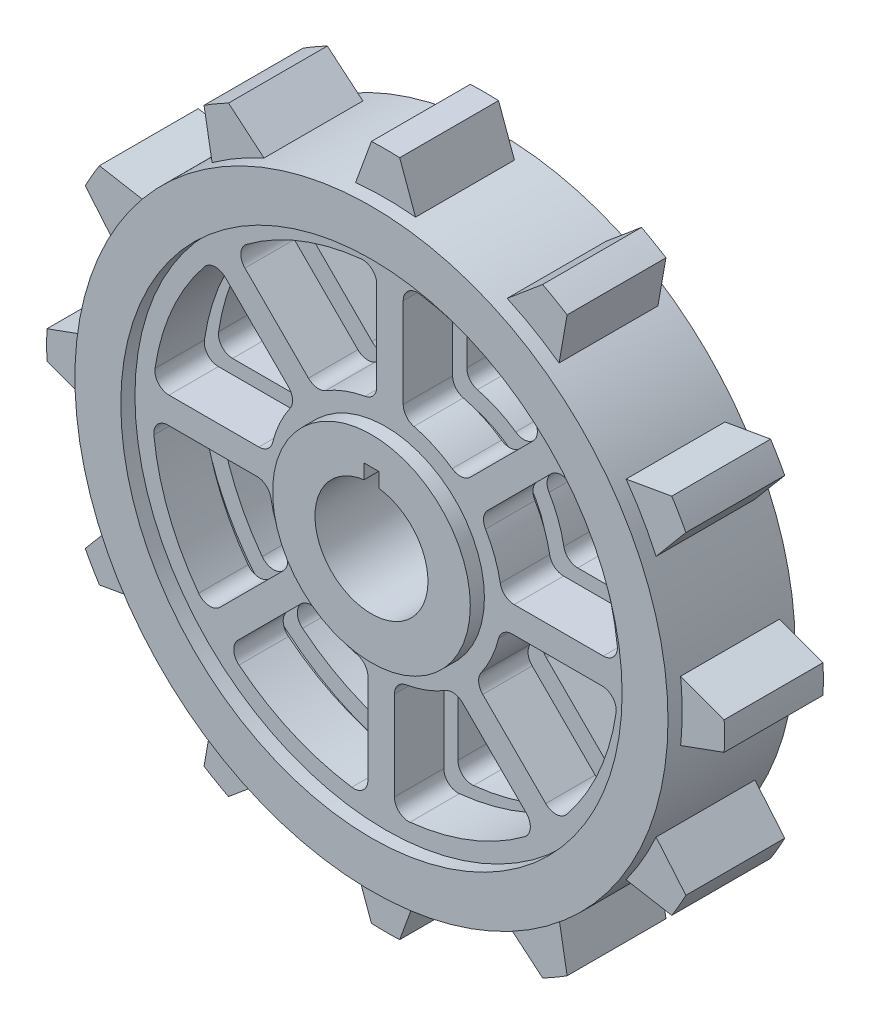
SolidWorks part; units mm, degrees
ref_plane "Front Plane" through (0, 0, 0) normal (0, 0, 1) x (1, 0, 0)
ref_plane "Top Plane" through (0, 0, 0) normal (0, 1, 0) x (1, 0, 0)
ref_plane "Right Plane" through (0, 0, 0) normal (1, 0, 0) x (0, 0, -1)
sketch "Sketch3" plane through (0, 0, 0) normal (0, 0, 1) x (1, 0, 0)
  circle A0 centre (0, 0) radius 21
  dimension "D1" = 42
extrude "Boss-Extrude2" add sketch "Sketch3" along normal mid plane 9
sketch "Sketch4" plane through (0, 0, 4.5) normal (0, 0, 1) x (1, 0, 0)
  line L0 (0, 0) -> (0, 4) construction
  line L1 (-0.525, 3.9654) -> (-0.525, 5)
  line L2 (-0.525, 5) -> (0.525, 5)
  line L3 (0.525, 5) -> (0.525, 3.9654)
  circle A0 centre (0, 0) radius 4
  dimension "D1" = 8
  dimension "D2" = 5
  dimension "1.05" = 1.05
extrude "Cut-Extrude1" cut sketch "Sketch4" against normal through all contours A0 | A0 L3 L2 L1 region at (0, 4.4942, 4.5) region at (0, 0, 4.5)
sketch "Sketch5" plane through (0, 0, 0) normal (0, 0, 1) x (1, 0, 0)
  circle A0 centre (0, 0) radius 17.75
  circle A1 centre (0, 0) radius 7
  circle A2 centre (0, 0) radius 21 construction
  dimension "D1" = 14
  dimension "D2" = 3.25
extrude "Cut-Extrude5" cut sketch "Sketch5" against normal blind 1
sketch "Sketch6" plane through (0, 0, 4.5) normal (0, 0, 1) x (1, 0, 0)
  circle A0 centre (0, 0) radius 7
  circle A1 centre (0, 0) radius 17.75
  circle A2 centre (0, 0) radius 21 construction
  dimension "D1" = 14
  dimension "D2" = 3.25
extrude "Cut-Extrude6" cut sketch "Sketch6" against normal blind 1
mirror "Mirror2" about plane through (0, 0, 0) normal (0, 0, 1) of "Cut-Extrude6"
sketch "Sketch7" plane through (0, 0, 3.5) normal (0, 0, 1) x (1, 0, 0)
  line L0 (0, 0) -> (0, 17.75) construction
  line L1 (0, 0) -> (12.5511, 12.5511) construction
  line L2 (1.25, 16.4526) -> (1.25, 8.1548)
  line L3 (11.2169, 12.1008) -> (5.3749, 6.2588)
  circle A0 centre (0, 0) radius 17.75 construction
  circle A1 centre (0, 0) radius 17.75 construction
  circle A3 centre (0, 0) radius 8.25
  circle A4 centre (0, 0) radius 7 construction
  circle A6 centre (0, 0) radius 16.5
  dimension "D2" = 1.25
  dimension "D3" = 1.25
  dimension "D1" = 45
  dimension "D4" = 1.25
  dimension "D5" = 1.25
extrude "Cut-Extrude7" cut sketch "Sketch7" against normal through all contours L3 A6 L2 A3 region at (5.1521, 11.633, 3.5)
fillet "Fillet1" radius 1 8 edges at (1.25, 16.4526, -2.25) (1.25, 16.4526, 1.75) (11.2169, 12.1008, 1.75) (11.2169, 12.1008, -2.25) (5.3749, 6.2588, 1.75) (5.3749, 6.2588, -2.25) (1.25, 8.1548, -2.25) (1.25, 8.1548, 1.75)
pattern_circular "CirPattern1" count 8 over 360 about axis through (0, 0, 4.5) along (0, 0, 1) of "Fillet1", "Cut-Extrude7"
sketch "Sketch8" plane through (0, 0, 3.5) normal (0, 0, 1) x (1, 0, 0)
  line L0 (0, 0) -> (0, 21) construction
  line L1 (-1, 23.9792) -> (-2.1235, 20.8924)
  line L2 (1, 23.9792) -> (2.1235, 20.8924)
  circle A0 centre (0, 0) radius 21 construction
  arc A1 (1, 23.9792) -> (-1, 23.9792) centre (0, 0) ccw
  arc A2 (2.1235, 20.8924) -> (-2.1235, 20.8924) centre (0, 0) ccw
  dimension "D1" = 3
  dimension "D2" = 40
  dimension "D3" = 2
extrude "Boss-Extrude3" add sketch "Sketch8" against normal blind 7
pattern_circular "CirPattern2" count 12 over 360 about axis through (0, 0, 4.5) along (0, 0, 1) of "Boss-Extrude3"
